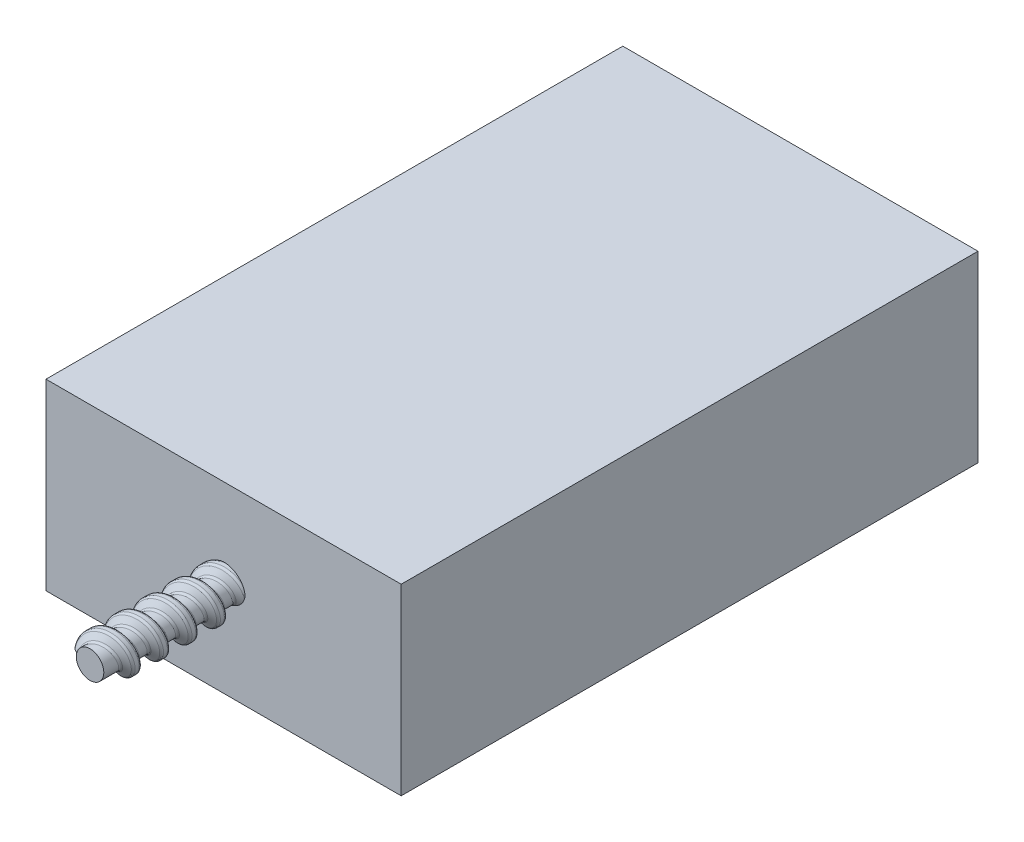
SolidWorks part; units mm, degrees
ref_plane "Front Plane" through (0, 0, 0) normal (0, 0, 1) x (1, 0, 0)
ref_plane "Top Plane" through (0, 0, 0) normal (0, 1, 0) x (1, 0, 0)
ref_plane "Right Plane" through (0, 0, 0) normal (1, 0, 0) x (0, 0, -1)
sketch "Sketch1" plane through (0, 0, 0) normal (0, 0, 1) x (1, 0, 0)
  line L1 (0, 0) -> (63.5, 0)
  line L2 (0, 0) -> (0, 32.766)
  line L3 (0, 32.766) -> (63.5, 32.766)
  line L4 (63.5, 0) -> (63.5, 32.766)
  dimension "D1" = 63.5
  dimension "D2" = 32.766
extrude "Boss-Extrude1" add sketch "Sketch1" against normal blind 127
sketch "Sketch2" plane through (0, 0, 0) normal (0, 0, 1) x (1, 0, 0)
  line L0 (63.5, 32.766) -> (0, 32.766) construction
  line L1 (63.5, 0) -> (63.5, 32.766) construction
  line L3 (0, 32.766) -> (63.5, 32.766)
  line L4 (0, 32.766) -> (0, 0)
  line L5 (0, 0) -> (63.5, 0)
  line L6 (63.5, 32.766) -> (63.5, 0)
  circle A0 centre (31.75, 16.383) radius 2.4574
  dimension "D1" = 4.9149
  dimension "D2" = 16.383
  dimension "D3" = 31.75
extrude "Cut-Extrude2" cut sketch "Sketch2" against normal blind 23.876
thread "Thread2" pitch 5.08 method extrude profile "Thread Profile2" start angle 0, offset 0, length 0, pitch 5.08, diameter 4.9149
ref_plane "Plane2" through (29.2926, 16.383, 0) normal (0, -1, 0) x (-1, 0, 0)
sketch "Thread Profile2" plane through (29.2926, 16.383, 0) normal (0, -1, 0) x (-1, 0, 0)
  line L0 (0, 0) -> (0, 5.08) construction
  line L1 (0, 0) -> (0, 3.6346)
  line L2 (0.508, 3.6346) -> (1.524, 3.6346) construction
  line L3 (1.524, 2.1681) -> (1.524, 1.4665)
  line L4 (1.27, 2.6081) -> (0.254, 3.1946)
  line L5 (1.27, 1.0265) -> (0.254, 0.4399)
  line L6 (0.508, 0) -> (1.524, 0) construction
  arc A0 (0.254, 3.1946) -> (0, 3.6346) centre (0.508, 3.6346) cw
  arc A1 (0.254, 0.4399) -> (0, 0) centre (0.508, 0) ccw
  arc A2 (1.524, 1.4665) -> (1.27, 1.0265) centre (1.016, 1.4665) cw
  arc A3 (1.524, 2.1681) -> (1.27, 2.6081) centre (1.016, 2.1681) ccw
  point P10 (1.524, 2.4614)
  point P17 (1.524, 1.1732)
  point P18 (0, 3.3413)
  point P19 (0, 0.2933)
  point P20 (0, 0)
  dimension "RootFillet1" = 0.508
  dimension "RootFillet2" = 0.508
  dimension "CrestFillet2" = 0.508
  dimension "CrestFillet1" = 0.508
  dimension "Pitch" = 5.08
  dimension "Angle1" = 30
  dimension "Angle2" = 30
  dimension "a" = 3.048
  dimension "b" = 1.524
  dimension "c" = 1.2882
